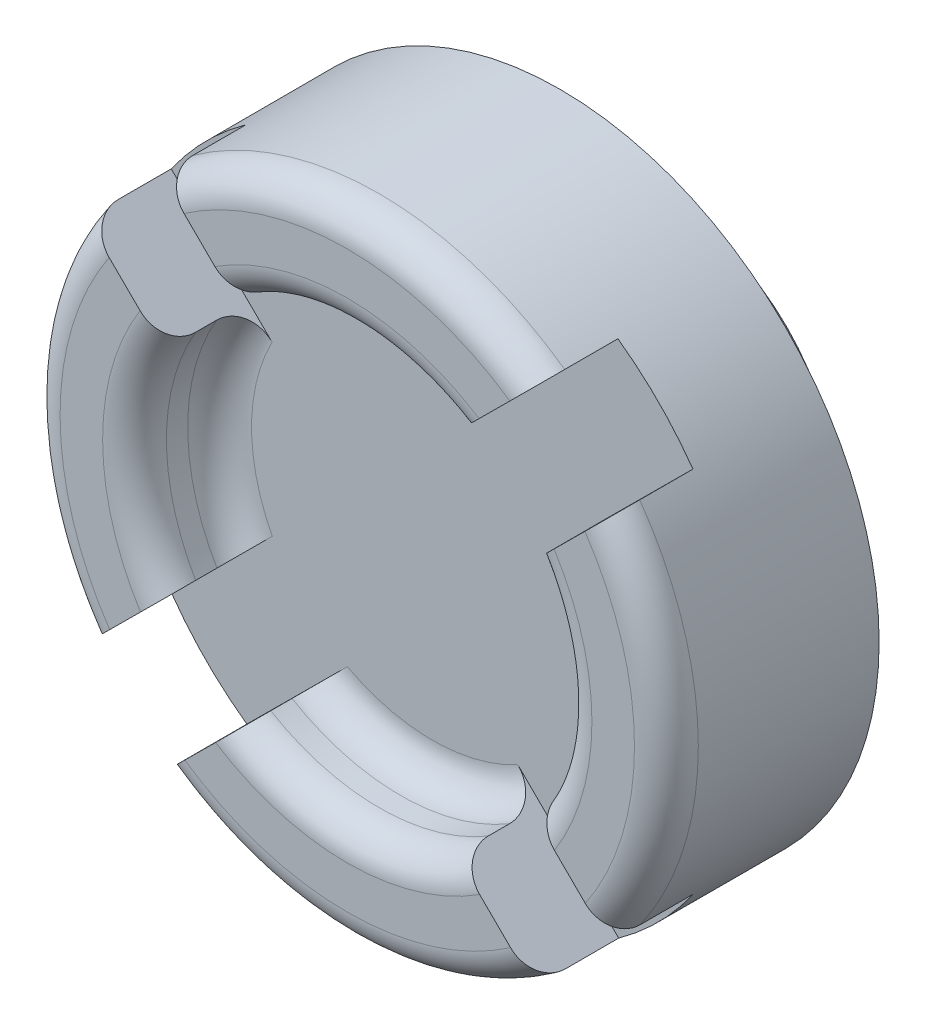
SolidWorks part; units mm, degrees
ref_plane "前视基准面" through (0, 0, 0) normal (0, 0, 1) x (1, 0, 0)
ref_plane "上视基准面" through (0, 0, 0) normal (0, 1, 0) x (1, 0, 0)
ref_plane "右视基准面" through (0, 0, 0) normal (1, 0, 0) x (0, 0, -1)
other "Configuration Table"
sketch "草图1" plane through (0, 0, 0) normal (0, 0, 1) x (1, 0, 0)
  line L0 (-1.0607, 0) -> (1.0607, 0) construction
  line L1 (0, -1.0607) -> (0, 1.0607) construction
  line L2 (1.4849, 0) -> (0, 1.4849)
  line L3 (1.4849, 0) -> (0, -1.4849)
  line L4 (0, 1.4849) -> (-1.4849, 0)
  line L5 (0, -1.4849) -> (-1.4849, 0)
  line L6 (1.4849, 0) -> (-1.4849, 0) construction
  line L7 (0, 1.4849) -> (0, -1.4849) construction
  line L8 (-1.2021, 0.1414) -> (-0.1414, 1.2021) construction
  line L9 (0.1414, 1.2021) -> (1.2021, 0.1414) construction
  circle A0 centre (0, 0) radius 1.6
  point P9 (0, 0)
  dimension "D1" = 0.1
  dimension "D2" = 0.1
extrude "凸台-拉伸1" add sketch "草图1" against normal blind 2
sketch "草图2" plane through (0, 0, 0) normal (0, 0, 1) x (1, 0, 0)
  circle A0 centre (0, 0) radius 3
  dimension "D1" = 6
extrude "凸台-拉伸2" add sketch "草图2" along normal blind 1
sketch "草图3" plane through (0, 0, 0) normal (0, 0, -1) x (-1, 0, 0)
  circle A0 centre (0, 0) radius 3 construction
  circle A1 centre (0, 0) radius 1.6 construction
  circle A2 centre (0, 0) radius 3
  circle A3 centre (0, 0) radius 1.6
extrude "凸台-拉伸3" add sketch "草图3" along normal blind 1
sketch "草图4" plane through (0, 0, 1) normal (0, 0, 1) x (1, 0, 0)
  line L0 (0, 0) -> (-4.1431, 4.1431) construction
  line L1 (0, 0) -> (4.1431, 4.1431) construction
  line L2 (0, 0) -> (4.1431, -4.1431) construction
  line L3 (0, 0) -> (-4.1431, -4.1431) construction
  line L4 (2.8402, -2.1056) -> (2.137, -2.8166)
  line L5 (2.8402, -2.1056) -> (0.71, 0.0011)
  line L6 (2.137, -2.8166) -> (0.0011, -0.7043)
  line L7 (-2.137, 2.8166) -> (-2.8402, 2.1056)
  line L8 (2.8402, -2.1056) -> (-2.8402, 2.1056) construction
  line L9 (2.137, -2.8166) -> (-2.137, 2.8166) construction
  line L10 (-2.8337, -2.1142) -> (-2.1284, -2.8231)
  line L11 (-2.8337, -2.1142) -> (-0.71, -0.0011)
  line L12 (-2.1284, -2.8231) -> (0.0011, -0.7043)
  line L13 (2.1284, 2.8231) -> (2.8337, 2.1142)
  line L14 (-2.8337, -2.1142) -> (2.8337, 2.1142) construction
  line L15 (-2.1284, -2.8231) -> (2.1284, 2.8231) construction
  line L16 (-0.0011, 0.7043) -> (-2.137, 2.8166)
  line L17 (-0.0011, 0.7043) -> (2.1284, 2.8231)
  line L18 (-0.71, -0.0011) -> (-2.8402, 2.1056)
  line L19 (0.71, 0.0011) -> (2.8337, 2.1142)
  dimension "D1" = 1
  dimension "D2" = 1
  dimension "D3" = 7
  dimension "D4" = 7
extrude "切除-拉伸1" cut sketch "草图4" against normal blind 0.8
sketch "草图5" plane through (0, 0, 1) normal (0, 0, 1) x (1, 0, 0)
  circle A0 centre (0, 0) radius 2
  dimension "D1" = 4
extrude "切除-拉伸2" cut sketch "草图5" against normal blind 0.8
fillet "圆角1" radius 0.3 8 edges at (0.0046, -3, 1) (-3, -0.0046, 1) (-0.0046, 3, 1) (3, 0.0046, 1) (0.003, -2, 1) (-2, -0.003, 1) (-0.003, 2, 1) (2, 0.003, 1)
fillet "圆角2" radius 0.3 4 edges at (0.003, -2, 0.2) (2, 0.003, 0.2) (-2, -0.003, 0.2) (-0.003, 2, 0.2)
chamfer "倒角2" distance 1 angle 45 1 edges at (-1.6, 0, -1)
sketch "草图6" plane through (0, 0, 0) normal (0, 0, -1) x (-1, 0, 0)
  line L0 (0, 1.4849) -> (1.4849, 0)
  line L1 (1.4849, 0) -> (0, -1.4849)
  line L2 (0, -1.4849) -> (-1.4849, 0)
  line L3 (-1.4849, 0) -> (0, 1.4849)
extrude "凸台-拉伸4" add sketch "草图6" along normal blind 0.5
